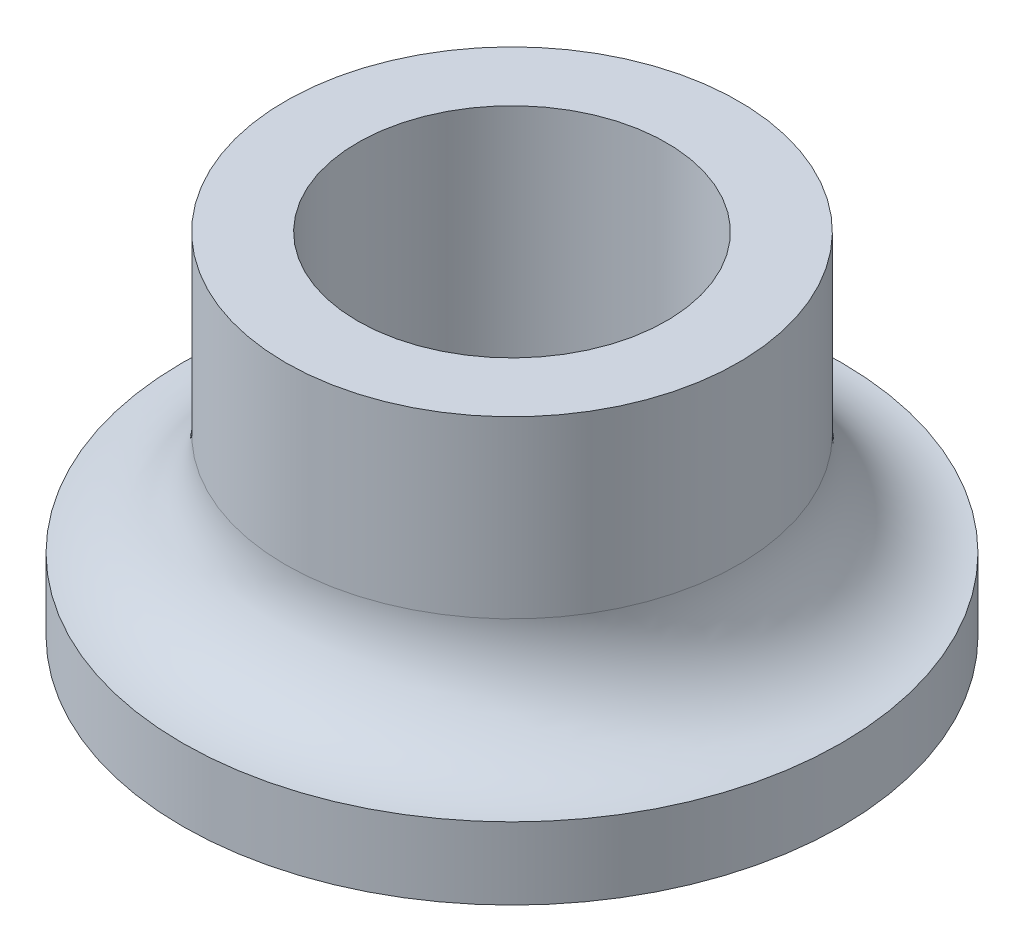
SolidWorks part; units mm, degrees
ref_plane "前基準面" through (0, 0, 0) normal (0, 0, 1) x (1, 0, 0)
ref_plane "上基準面" through (0, 0, 0) normal (0, 1, 0) x (1, 0, 0)
ref_plane "右基準面" through (0, 0, 0) normal (1, 0, 0) x (0, 0, -1)
sketch "草圖1" plane through (0, 0, 0) normal (0, 1, 0) x (1, 0, 0)
  circle A0 centre (0, 0) radius 16
  circle A1 centre (0, 0) radius 7.5
  dimension "D1" = 32
  dimension "D2" = 15
extrude "填料-伸長1" add sketch "草圖1" along normal blind 3.5
sketch "草圖2" plane through (0, 3.5, 0) normal (0, 1, 0) x (1, 0, 0)
  circle A0 centre (0, 0) radius 11
  circle A1 centre (0, 0) radius 7.5 construction
  circle A2 centre (0, 0) radius 7.5
  point P3 (0, 0)
  dimension "D1" = 22
extrude "填料-伸長2" add sketch "草圖2" along normal blind 13.5
fillet "圓角1" radius 5 1 edges at (0, 3.5, 11)
